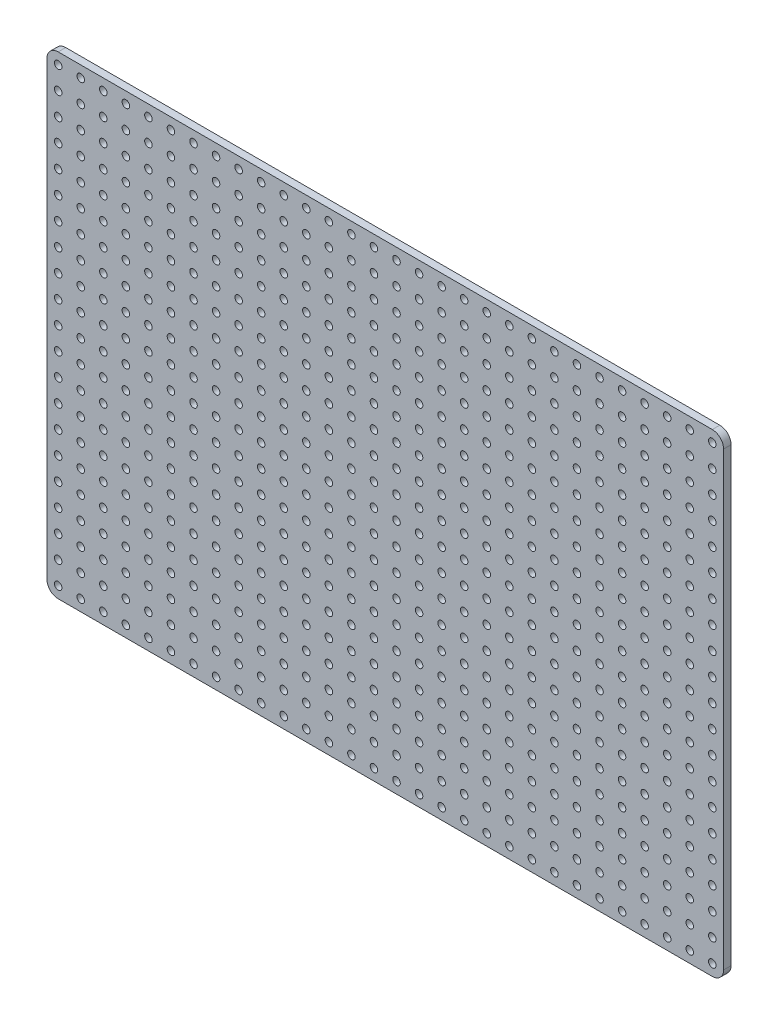
SolidWorks part; units mm, degrees
ref_plane "Alzado" through (0, 0, 0) normal (0, 0, 1) x (1, 0, 0)
ref_plane "Planta" through (0, 0, 0) normal (0, 1, 0) x (1, 0, 0)
ref_plane "Vista lateral" through (0, 0, 0) normal (1, 0, 0) x (0, 0, -1)
sketch "Model" plane through (0, 0, 0) normal (0, 0, 1) x (1, 0, 0)
  line L0 (256.4291, 489.7422) -> (517.4291, 489.7422)
  line L1 (256.4291, 300.7422) -> (517.4291, 300.7422)
  line L2 (251.9291, 305.2422) -> (251.9291, 485.2422)
  line L3 (521.9291, 485.2422) -> (521.9291, 305.2422)
  arc A0 (521.9291, 485.2422) -> (517.4291, 489.7422) centre (517.4291, 485.2422) ccw
  arc A1 (256.4291, 489.7422) -> (251.9291, 485.2422) centre (256.4291, 485.2422) ccw
  arc A2 (517.4291, 300.7422) -> (521.9291, 305.2422) centre (517.4291, 305.2422) ccw
  arc A3 (251.9291, 305.2422) -> (256.4291, 300.7422) centre (256.4291, 305.2422) ccw
  circle A4 centre (256.4291, 485.2422) radius 1.5
  circle A5 centre (256.4291, 476.2422) radius 1.5
  circle A6 centre (256.4291, 467.2422) radius 1.5
  circle A7 centre (256.4291, 458.2422) radius 1.5
  circle A8 centre (256.4291, 449.2422) radius 1.5
  circle A9 centre (256.4291, 440.2422) radius 1.5
  circle A10 centre (256.4291, 431.2422) radius 1.5
  circle A11 centre (256.4291, 422.2422) radius 1.5
  circle A12 centre (256.4291, 413.2422) radius 1.5
  circle A13 centre (256.4291, 404.2422) radius 1.5
  circle A14 centre (256.4291, 395.2422) radius 1.5
  circle A15 centre (256.4291, 386.2422) radius 1.5
  circle A16 centre (256.4291, 377.2422) radius 1.5
  circle A17 centre (256.4291, 368.2422) radius 1.5
  circle A18 centre (256.4291, 359.2422) radius 1.5
  circle A19 centre (256.4291, 350.2422) radius 1.5
  circle A20 centre (256.4291, 341.2422) radius 1.5
  circle A21 centre (256.4291, 332.2422) radius 1.5
  circle A22 centre (256.4291, 323.2422) radius 1.5
  circle A23 centre (256.4291, 314.2422) radius 1.5
  circle A24 centre (256.4291, 305.2422) radius 1.5
  circle A25 centre (265.4291, 485.2422) radius 1.5
  circle A26 centre (265.4291, 476.2422) radius 1.5
  circle A27 centre (265.4291, 467.2422) radius 1.5
  circle A28 centre (265.4291, 458.2422) radius 1.5
  circle A29 centre (265.4291, 449.2422) radius 1.5
  circle A30 centre (265.4291, 440.2422) radius 1.5
  circle A31 centre (265.4291, 431.2422) radius 1.5
  circle A32 centre (265.4291, 422.2422) radius 1.5
  circle A33 centre (265.4291, 413.2422) radius 1.5
  circle A34 centre (265.4291, 404.2422) radius 1.5
  circle A35 centre (265.4291, 395.2422) radius 1.5
  circle A36 centre (265.4291, 386.2422) radius 1.5
  circle A37 centre (265.4291, 377.2422) radius 1.5
  circle A38 centre (265.4291, 368.2422) radius 1.5
  circle A39 centre (265.4291, 359.2422) radius 1.5
  circle A40 centre (265.4291, 350.2422) radius 1.5
  circle A41 centre (265.4291, 341.2422) radius 1.5
  circle A42 centre (265.4291, 332.2422) radius 1.5
  circle A43 centre (265.4291, 323.2422) radius 1.5
  circle A44 centre (265.4291, 314.2422) radius 1.5
  circle A45 centre (265.4291, 305.2422) radius 1.5
  circle A46 centre (274.4291, 485.2422) radius 1.5
  circle A47 centre (274.4291, 476.2422) radius 1.5
  circle A48 centre (274.4291, 467.2422) radius 1.5
  circle A49 centre (274.4291, 458.2422) radius 1.5
  circle A50 centre (274.4291, 449.2422) radius 1.5
  circle A51 centre (274.4291, 440.2422) radius 1.5
  circle A52 centre (274.4291, 431.2422) radius 1.5
  circle A53 centre (274.4291, 422.2422) radius 1.5
  circle A54 centre (274.4291, 413.2422) radius 1.5
  circle A55 centre (274.4291, 404.2422) radius 1.5
  circle A56 centre (274.4291, 395.2422) radius 1.5
  circle A57 centre (274.4291, 386.2422) radius 1.5
  circle A58 centre (274.4291, 377.2422) radius 1.5
  circle A59 centre (274.4291, 368.2422) radius 1.5
  circle A60 centre (274.4291, 359.2422) radius 1.5
  circle A61 centre (274.4291, 350.2422) radius 1.5
  circle A62 centre (274.4291, 341.2422) radius 1.5
  circle A63 centre (274.4291, 332.2422) radius 1.5
  circle A64 centre (274.4291, 323.2422) radius 1.5
  circle A65 centre (274.4291, 314.2422) radius 1.5
  circle A66 centre (274.4291, 305.2422) radius 1.5
  circle A67 centre (283.4291, 485.2422) radius 1.5
  circle A68 centre (283.4291, 476.2422) radius 1.5
  circle A69 centre (283.4291, 467.2422) radius 1.5
  circle A70 centre (283.4291, 458.2422) radius 1.5
  circle A71 centre (283.4291, 449.2422) radius 1.5
  circle A72 centre (283.4291, 440.2422) radius 1.5
  circle A73 centre (283.4291, 431.2422) radius 1.5
  circle A74 centre (283.4291, 422.2422) radius 1.5
  circle A75 centre (283.4291, 413.2422) radius 1.5
  circle A76 centre (283.4291, 404.2422) radius 1.5
  circle A77 centre (283.4291, 395.2422) radius 1.5
  circle A78 centre (283.4291, 386.2422) radius 1.5
  circle A79 centre (283.4291, 377.2422) radius 1.5
  circle A80 centre (283.4291, 368.2422) radius 1.5
  circle A81 centre (283.4291, 359.2422) radius 1.5
  circle A82 centre (283.4291, 350.2422) radius 1.5
  circle A83 centre (283.4291, 341.2422) radius 1.5
  circle A84 centre (283.4291, 332.2422) radius 1.5
  circle A85 centre (283.4291, 323.2422) radius 1.5
  circle A86 centre (283.4291, 314.2422) radius 1.5
  circle A87 centre (283.4291, 305.2422) radius 1.5
  circle A88 centre (292.4291, 485.2422) radius 1.5
  circle A89 centre (292.4291, 476.2422) radius 1.5
  circle A90 centre (292.4291, 467.2422) radius 1.5
  circle A91 centre (292.4291, 458.2422) radius 1.5
  circle A92 centre (292.4291, 449.2422) radius 1.5
  circle A93 centre (292.4291, 440.2422) radius 1.5
  circle A94 centre (292.4291, 431.2422) radius 1.5
  circle A95 centre (292.4291, 422.2422) radius 1.5
  circle A96 centre (292.4291, 413.2422) radius 1.5
  circle A97 centre (292.4291, 404.2422) radius 1.5
  circle A98 centre (292.4291, 395.2422) radius 1.5
  circle A99 centre (292.4291, 386.2422) radius 1.5
  circle A100 centre (292.4291, 377.2422) radius 1.5
  circle A101 centre (292.4291, 368.2422) radius 1.5
  circle A102 centre (292.4291, 359.2422) radius 1.5
  circle A103 centre (292.4291, 350.2422) radius 1.5
  circle A104 centre (292.4291, 341.2422) radius 1.5
  circle A105 centre (292.4291, 332.2422) radius 1.5
  circle A106 centre (292.4291, 323.2422) radius 1.5
  circle A107 centre (292.4291, 314.2422) radius 1.5
  circle A108 centre (292.4291, 305.2422) radius 1.5
  circle A109 centre (301.4291, 485.2422) radius 1.5
  circle A110 centre (301.4291, 476.2422) radius 1.5
  circle A111 centre (301.4291, 467.2422) radius 1.5
  circle A112 centre (301.4291, 458.2422) radius 1.5
  circle A113 centre (301.4291, 449.2422) radius 1.5
  circle A114 centre (301.4291, 440.2422) radius 1.5
  circle A115 centre (301.4291, 431.2422) radius 1.5
  circle A116 centre (301.4291, 422.2422) radius 1.5
  circle A117 centre (301.4291, 413.2422) radius 1.5
  circle A118 centre (301.4291, 404.2422) radius 1.5
  circle A119 centre (301.4291, 395.2422) radius 1.5
  circle A120 centre (301.4291, 386.2422) radius 1.5
  circle A121 centre (301.4291, 377.2422) radius 1.5
  circle A122 centre (301.4291, 368.2422) radius 1.5
  circle A123 centre (301.4291, 359.2422) radius 1.5
  circle A124 centre (301.4291, 350.2422) radius 1.5
  circle A125 centre (301.4291, 341.2422) radius 1.5
  circle A126 centre (301.4291, 332.2422) radius 1.5
  circle A127 centre (301.4291, 323.2422) radius 1.5
  circle A128 centre (301.4291, 314.2422) radius 1.5
  circle A129 centre (301.4291, 305.2422) radius 1.5
  circle A130 centre (310.4291, 485.2422) radius 1.5
  circle A131 centre (310.4291, 476.2422) radius 1.5
  circle A132 centre (310.4291, 467.2422) radius 1.5
  circle A133 centre (310.4291, 458.2422) radius 1.5
  circle A134 centre (310.4291, 449.2422) radius 1.5
  circle A135 centre (310.4291, 440.2422) radius 1.5
  circle A136 centre (310.4291, 431.2422) radius 1.5
  circle A137 centre (310.4291, 422.2422) radius 1.5
  circle A138 centre (310.4291, 413.2422) radius 1.5
  circle A139 centre (310.4291, 404.2422) radius 1.5
  circle A140 centre (310.4291, 395.2422) radius 1.5
  circle A141 centre (310.4291, 386.2422) radius 1.5
  circle A142 centre (310.4291, 377.2422) radius 1.5
  circle A143 centre (310.4291, 368.2422) radius 1.5
  circle A144 centre (310.4291, 359.2422) radius 1.5
  circle A145 centre (310.4291, 350.2422) radius 1.5
  circle A146 centre (310.4291, 341.2422) radius 1.5
  circle A147 centre (310.4291, 332.2422) radius 1.5
  circle A148 centre (310.4291, 323.2422) radius 1.5
  circle A149 centre (310.4291, 314.2422) radius 1.5
  circle A150 centre (310.4291, 305.2422) radius 1.5
  circle A151 centre (319.4291, 485.2422) radius 1.5
  circle A152 centre (319.4291, 476.2422) radius 1.5
  circle A153 centre (319.4291, 467.2422) radius 1.5
  circle A154 centre (319.4291, 458.2422) radius 1.5
  circle A155 centre (319.4291, 449.2422) radius 1.5
  circle A156 centre (319.4291, 440.2422) radius 1.5
  circle A157 centre (319.4291, 431.2422) radius 1.5
  circle A158 centre (319.4291, 422.2422) radius 1.5
  circle A159 centre (319.4291, 413.2422) radius 1.5
  circle A160 centre (319.4291, 404.2422) radius 1.5
  circle A161 centre (319.4291, 395.2422) radius 1.5
  circle A162 centre (319.4291, 386.2422) radius 1.5
  circle A163 centre (319.4291, 377.2422) radius 1.5
  circle A164 centre (319.4291, 368.2422) radius 1.5
  circle A165 centre (319.4291, 359.2422) radius 1.5
  circle A166 centre (319.4291, 350.2422) radius 1.5
  circle A167 centre (319.4291, 341.2422) radius 1.5
  circle A168 centre (319.4291, 332.2422) radius 1.5
  circle A169 centre (319.4291, 323.2422) radius 1.5
  circle A170 centre (319.4291, 314.2422) radius 1.5
  circle A171 centre (319.4291, 305.2422) radius 1.5
  circle A172 centre (328.4291, 485.2422) radius 1.5
  circle A173 centre (328.4291, 476.2422) radius 1.5
  circle A174 centre (328.4291, 467.2422) radius 1.5
  circle A175 centre (328.4291, 458.2422) radius 1.5
  circle A176 centre (328.4291, 449.2422) radius 1.5
  circle A177 centre (328.4291, 440.2422) radius 1.5
  circle A178 centre (328.4291, 431.2422) radius 1.5
  circle A179 centre (328.4291, 422.2422) radius 1.5
  circle A180 centre (328.4291, 413.2422) radius 1.5
  circle A181 centre (328.4291, 404.2422) radius 1.5
  circle A182 centre (328.4291, 395.2422) radius 1.5
  circle A183 centre (328.4291, 386.2422) radius 1.5
  circle A184 centre (328.4291, 377.2422) radius 1.5
  circle A185 centre (328.4291, 368.2422) radius 1.5
  circle A186 centre (328.4291, 359.2422) radius 1.5
  circle A187 centre (328.4291, 350.2422) radius 1.5
  circle A188 centre (328.4291, 341.2422) radius 1.5
  circle A189 centre (328.4291, 332.2422) radius 1.5
  circle A190 centre (328.4291, 323.2422) radius 1.5
  circle A191 centre (328.4291, 314.2422) radius 1.5
  circle A192 centre (328.4291, 305.2422) radius 1.5
  circle A193 centre (337.4291, 485.2422) radius 1.5
  circle A194 centre (337.4291, 476.2422) radius 1.5
  circle A195 centre (337.4291, 467.2422) radius 1.5
  circle A196 centre (337.4291, 458.2422) radius 1.5
  circle A197 centre (337.4291, 449.2422) radius 1.5
  circle A198 centre (337.4291, 440.2422) radius 1.5
  circle A199 centre (337.4291, 431.2422) radius 1.5
  circle A200 centre (337.4291, 422.2422) radius 1.5
  circle A201 centre (337.4291, 413.2422) radius 1.5
  circle A202 centre (337.4291, 404.2422) radius 1.5
  circle A203 centre (337.4291, 395.2422) radius 1.5
  circle A204 centre (337.4291, 386.2422) radius 1.5
  circle A205 centre (337.4291, 377.2422) radius 1.5
  circle A206 centre (337.4291, 368.2422) radius 1.5
  circle A207 centre (337.4291, 359.2422) radius 1.5
  circle A208 centre (337.4291, 350.2422) radius 1.5
  circle A209 centre (337.4291, 341.2422) radius 1.5
  circle A210 centre (337.4291, 332.2422) radius 1.5
  circle A211 centre (337.4291, 323.2422) radius 1.5
  circle A212 centre (337.4291, 314.2422) radius 1.5
  circle A213 centre (337.4291, 305.2422) radius 1.5
  circle A214 centre (346.4291, 485.2422) radius 1.5
  circle A215 centre (346.4291, 476.2422) radius 1.5
  circle A216 centre (346.4291, 467.2422) radius 1.5
  circle A217 centre (346.4291, 458.2422) radius 1.5
  circle A218 centre (346.4291, 449.2422) radius 1.5
  circle A219 centre (346.4291, 440.2422) radius 1.5
  circle A220 centre (346.4291, 431.2422) radius 1.5
  circle A221 centre (346.4291, 422.2422) radius 1.5
  circle A222 centre (346.4291, 413.2422) radius 1.5
  circle A223 centre (346.4291, 404.2422) radius 1.5
  circle A224 centre (346.4291, 395.2422) radius 1.5
  circle A225 centre (346.4291, 386.2422) radius 1.5
  circle A226 centre (346.4291, 377.2422) radius 1.5
  circle A227 centre (346.4291, 368.2422) radius 1.5
  circle A228 centre (346.4291, 359.2422) radius 1.5
  circle A229 centre (346.4291, 350.2422) radius 1.5
  circle A230 centre (346.4291, 341.2422) radius 1.5
  circle A231 centre (346.4291, 332.2422) radius 1.5
  circle A232 centre (346.4291, 323.2422) radius 1.5
  circle A233 centre (346.4291, 314.2422) radius 1.5
  circle A234 centre (346.4291, 305.2422) radius 1.5
  circle A235 centre (355.4291, 485.2422) radius 1.5
  circle A236 centre (355.4291, 476.2422) radius 1.5
  circle A237 centre (355.4291, 467.2422) radius 1.5
  circle A238 centre (355.4291, 458.2422) radius 1.5
  circle A239 centre (355.4291, 449.2422) radius 1.5
  circle A240 centre (355.4291, 440.2422) radius 1.5
  circle A241 centre (355.4291, 431.2422) radius 1.5
  circle A242 centre (355.4291, 422.2422) radius 1.5
  circle A243 centre (355.4291, 413.2422) radius 1.5
  circle A244 centre (355.4291, 404.2422) radius 1.5
  circle A245 centre (355.4291, 395.2422) radius 1.5
  circle A246 centre (355.4291, 386.2422) radius 1.5
  circle A247 centre (355.4291, 377.2422) radius 1.5
  circle A248 centre (355.4291, 368.2422) radius 1.5
  circle A249 centre (355.4291, 359.2422) radius 1.5
  circle A250 centre (355.4291, 350.2422) radius 1.5
  circle A251 centre (355.4291, 341.2422) radius 1.5
  circle A252 centre (355.4291, 332.2422) radius 1.5
  circle A253 centre (355.4291, 323.2422) radius 1.5
  circle A254 centre (355.4291, 314.2422) radius 1.5
  circle A255 centre (355.4291, 305.2422) radius 1.5
  circle A256 centre (364.4291, 485.2422) radius 1.5
  circle A257 centre (364.4291, 476.2422) radius 1.5
  circle A258 centre (364.4291, 467.2422) radius 1.5
  circle A259 centre (364.4291, 458.2422) radius 1.5
  circle A260 centre (364.4291, 449.2422) radius 1.5
  circle A261 centre (364.4291, 440.2422) radius 1.5
  circle A262 centre (364.4291, 431.2422) radius 1.5
  circle A263 centre (364.4291, 422.2422) radius 1.5
  circle A264 centre (364.4291, 413.2422) radius 1.5
  circle A265 centre (364.4291, 404.2422) radius 1.5
  circle A266 centre (364.4291, 395.2422) radius 1.5
  circle A267 centre (364.4291, 386.2422) radius 1.5
  circle A268 centre (364.4291, 377.2422) radius 1.5
  circle A269 centre (364.4291, 368.2422) radius 1.5
  circle A270 centre (364.4291, 359.2422) radius 1.5
  circle A271 centre (364.4291, 350.2422) radius 1.5
  circle A272 centre (364.4291, 341.2422) radius 1.5
  circle A273 centre (364.4291, 332.2422) radius 1.5
  circle A274 centre (364.4291, 323.2422) radius 1.5
  circle A275 centre (364.4291, 314.2422) radius 1.5
  circle A276 centre (364.4291, 305.2422) radius 1.5
  circle A277 centre (373.4291, 485.2422) radius 1.5
  circle A278 centre (373.4291, 476.2422) radius 1.5
  circle A279 centre (373.4291, 467.2422) radius 1.5
  circle A280 centre (373.4291, 458.2422) radius 1.5
  circle A281 centre (373.4291, 449.2422) radius 1.5
  circle A282 centre (373.4291, 440.2422) radius 1.5
  circle A283 centre (373.4291, 431.2422) radius 1.5
  circle A284 centre (373.4291, 422.2422) radius 1.5
  circle A285 centre (373.4291, 413.2422) radius 1.5
  circle A286 centre (373.4291, 404.2422) radius 1.5
  circle A287 centre (373.4291, 395.2422) radius 1.5
  circle A288 centre (373.4291, 386.2422) radius 1.5
  circle A289 centre (373.4291, 377.2422) radius 1.5
  circle A290 centre (373.4291, 368.2422) radius 1.5
  circle A291 centre (373.4291, 359.2422) radius 1.5
  circle A292 centre (373.4291, 350.2422) radius 1.5
  circle A293 centre (373.4291, 341.2422) radius 1.5
  circle A294 centre (373.4291, 332.2422) radius 1.5
  circle A295 centre (373.4291, 323.2422) radius 1.5
  circle A296 centre (373.4291, 314.2422) radius 1.5
  circle A297 centre (373.4291, 305.2422) radius 1.5
  circle A298 centre (382.4291, 485.2422) radius 1.5
  circle A299 centre (382.4291, 476.2422) radius 1.5
  circle A300 centre (382.4291, 467.2422) radius 1.5
  circle A301 centre (382.4291, 458.2422) radius 1.5
  circle A302 centre (382.4291, 449.2422) radius 1.5
  circle A303 centre (382.4291, 440.2422) radius 1.5
  circle A304 centre (382.4291, 431.2422) radius 1.5
  circle A305 centre (382.4291, 422.2422) radius 1.5
  circle A306 centre (382.4291, 413.2422) radius 1.5
  circle A307 centre (382.4291, 404.2422) radius 1.5
  circle A308 centre (382.4291, 395.2422) radius 1.5
  circle A309 centre (382.4291, 386.2422) radius 1.5
  circle A310 centre (382.4291, 377.2422) radius 1.5
  circle A311 centre (382.4291, 368.2422) radius 1.5
  circle A312 centre (382.4291, 359.2422) radius 1.5
  circle A313 centre (382.4291, 350.2422) radius 1.5
  circle A314 centre (382.4291, 341.2422) radius 1.5
  circle A315 centre (382.4291, 332.2422) radius 1.5
  circle A316 centre (382.4291, 323.2422) radius 1.5
  circle A317 centre (382.4291, 314.2422) radius 1.5
  circle A318 centre (382.4291, 305.2422) radius 1.5
  circle A319 centre (391.4291, 485.2422) radius 1.5
  circle A320 centre (391.4291, 476.2422) radius 1.5
  circle A321 centre (391.4291, 467.2422) radius 1.5
  circle A322 centre (391.4291, 458.2422) radius 1.5
  circle A323 centre (391.4291, 449.2422) radius 1.5
  circle A324 centre (391.4291, 440.2422) radius 1.5
  circle A325 centre (391.4291, 431.2422) radius 1.5
  circle A326 centre (391.4291, 422.2422) radius 1.5
  circle A327 centre (391.4291, 413.2422) radius 1.5
  circle A328 centre (391.4291, 404.2422) radius 1.5
  circle A329 centre (391.4291, 395.2422) radius 1.5
  circle A330 centre (391.4291, 386.2422) radius 1.5
  circle A331 centre (391.4291, 377.2422) radius 1.5
  circle A332 centre (391.4291, 368.2422) radius 1.5
  circle A333 centre (391.4291, 359.2422) radius 1.5
  circle A334 centre (391.4291, 350.2422) radius 1.5
  circle A335 centre (391.4291, 341.2422) radius 1.5
  circle A336 centre (391.4291, 332.2422) radius 1.5
  circle A337 centre (391.4291, 323.2422) radius 1.5
  circle A338 centre (391.4291, 314.2422) radius 1.5
  circle A339 centre (391.4291, 305.2422) radius 1.5
  circle A340 centre (400.4291, 485.2422) radius 1.5
  circle A341 centre (400.4291, 476.2422) radius 1.5
  circle A342 centre (400.4291, 467.2422) radius 1.5
  circle A343 centre (400.4291, 458.2422) radius 1.5
  circle A344 centre (400.4291, 449.2422) radius 1.5
  circle A345 centre (400.4291, 440.2422) radius 1.5
  circle A346 centre (400.4291, 431.2422) radius 1.5
  circle A347 centre (400.4291, 422.2422) radius 1.5
  circle A348 centre (400.4291, 413.2422) radius 1.5
  circle A349 centre (400.4291, 404.2422) radius 1.5
  circle A350 centre (400.4291, 395.2422) radius 1.5
  circle A351 centre (400.4291, 386.2422) radius 1.5
  circle A352 centre (400.4291, 377.2422) radius 1.5
  circle A353 centre (400.4291, 368.2422) radius 1.5
  circle A354 centre (400.4291, 359.2422) radius 1.5
  circle A355 centre (400.4291, 350.2422) radius 1.5
  circle A356 centre (400.4291, 341.2422) radius 1.5
  circle A357 centre (400.4291, 332.2422) radius 1.5
  circle A358 centre (400.4291, 323.2422) radius 1.5
  circle A359 centre (400.4291, 314.2422) radius 1.5
  circle A360 centre (400.4291, 305.2422) radius 1.5
  circle A361 centre (409.4291, 485.2422) radius 1.5
  circle A362 centre (409.4291, 476.2422) radius 1.5
  circle A363 centre (409.4291, 467.2422) radius 1.5
  circle A364 centre (409.4291, 458.2422) radius 1.5
  circle A365 centre (409.4291, 449.2422) radius 1.5
  circle A366 centre (409.4291, 440.2422) radius 1.5
  circle A367 centre (409.4291, 431.2422) radius 1.5
  circle A368 centre (409.4291, 422.2422) radius 1.5
  circle A369 centre (409.4291, 413.2422) radius 1.5
  circle A370 centre (409.4291, 404.2422) radius 1.5
  circle A371 centre (409.4291, 395.2422) radius 1.5
  circle A372 centre (409.4291, 386.2422) radius 1.5
  circle A373 centre (409.4291, 377.2422) radius 1.5
  circle A374 centre (409.4291, 368.2422) radius 1.5
  circle A375 centre (409.4291, 359.2422) radius 1.5
  circle A376 centre (409.4291, 350.2422) radius 1.5
  circle A377 centre (409.4291, 341.2422) radius 1.5
  circle A378 centre (409.4291, 332.2422) radius 1.5
  circle A379 centre (409.4291, 323.2422) radius 1.5
  circle A380 centre (409.4291, 314.2422) radius 1.5
  circle A381 centre (409.4291, 305.2422) radius 1.5
  circle A382 centre (418.4291, 485.2422) radius 1.5
  circle A383 centre (418.4291, 476.2422) radius 1.5
  circle A384 centre (418.4291, 467.2422) radius 1.5
  circle A385 centre (418.4291, 458.2422) radius 1.5
  circle A386 centre (418.4291, 449.2422) radius 1.5
  circle A387 centre (418.4291, 440.2422) radius 1.5
  circle A388 centre (418.4291, 431.2422) radius 1.5
  circle A389 centre (418.4291, 422.2422) radius 1.5
  circle A390 centre (418.4291, 413.2422) radius 1.5
  circle A391 centre (418.4291, 404.2422) radius 1.5
  circle A392 centre (418.4291, 395.2422) radius 1.5
  circle A393 centre (418.4291, 386.2422) radius 1.5
  circle A394 centre (418.4291, 377.2422) radius 1.5
  circle A395 centre (418.4291, 368.2422) radius 1.5
  circle A396 centre (418.4291, 359.2422) radius 1.5
  circle A397 centre (418.4291, 350.2422) radius 1.5
  circle A398 centre (418.4291, 341.2422) radius 1.5
  circle A399 centre (418.4291, 332.2422) radius 1.5
  circle A400 centre (418.4291, 323.2422) radius 1.5
  circle A401 centre (418.4291, 314.2422) radius 1.5
  circle A402 centre (418.4291, 305.2422) radius 1.5
  circle A403 centre (427.4291, 485.2422) radius 1.5
  circle A404 centre (427.4291, 476.2422) radius 1.5
  circle A405 centre (427.4291, 467.2422) radius 1.5
  circle A406 centre (427.4291, 458.2422) radius 1.5
  circle A407 centre (427.4291, 449.2422) radius 1.5
  circle A408 centre (427.4291, 440.2422) radius 1.5
  circle A409 centre (427.4291, 431.2422) radius 1.5
  circle A410 centre (427.4291, 422.2422) radius 1.5
  circle A411 centre (427.4291, 413.2422) radius 1.5
  circle A412 centre (427.4291, 404.2422) radius 1.5
  circle A413 centre (427.4291, 395.2422) radius 1.5
  circle A414 centre (427.4291, 386.2422) radius 1.5
  circle A415 centre (427.4291, 377.2422) radius 1.5
  circle A416 centre (427.4291, 368.2422) radius 1.5
  circle A417 centre (427.4291, 359.2422) radius 1.5
  circle A418 centre (427.4291, 350.2422) radius 1.5
  circle A419 centre (427.4291, 341.2422) radius 1.5
  circle A420 centre (427.4291, 332.2422) radius 1.5
  circle A421 centre (427.4291, 323.2422) radius 1.5
  circle A422 centre (427.4291, 314.2422) radius 1.5
  circle A423 centre (427.4291, 305.2422) radius 1.5
  circle A424 centre (436.4291, 485.2422) radius 1.5
  circle A425 centre (436.4291, 476.2422) radius 1.5
  circle A426 centre (436.4291, 467.2422) radius 1.5
  circle A427 centre (436.4291, 458.2422) radius 1.5
  circle A428 centre (436.4291, 449.2422) radius 1.5
  circle A429 centre (436.4291, 440.2422) radius 1.5
  circle A430 centre (436.4291, 431.2422) radius 1.5
  circle A431 centre (436.4291, 422.2422) radius 1.5
  circle A432 centre (436.4291, 413.2422) radius 1.5
  circle A433 centre (436.4291, 404.2422) radius 1.5
  circle A434 centre (436.4291, 395.2422) radius 1.5
  circle A435 centre (436.4291, 386.2422) radius 1.5
  circle A436 centre (436.4291, 377.2422) radius 1.5
  circle A437 centre (436.4291, 368.2422) radius 1.5
  circle A438 centre (436.4291, 359.2422) radius 1.5
  circle A439 centre (436.4291, 350.2422) radius 1.5
  circle A440 centre (436.4291, 341.2422) radius 1.5
  circle A441 centre (436.4291, 332.2422) radius 1.5
  circle A442 centre (436.4291, 323.2422) radius 1.5
  circle A443 centre (436.4291, 314.2422) radius 1.5
  circle A444 centre (436.4291, 305.2422) radius 1.5
  circle A445 centre (445.4291, 485.2422) radius 1.5
  circle A446 centre (445.4291, 476.2422) radius 1.5
  circle A447 centre (445.4291, 467.2422) radius 1.5
  circle A448 centre (445.4291, 458.2422) radius 1.5
  circle A449 centre (445.4291, 449.2422) radius 1.5
  circle A450 centre (445.4291, 440.2422) radius 1.5
  circle A451 centre (445.4291, 431.2422) radius 1.5
  circle A452 centre (445.4291, 422.2422) radius 1.5
  circle A453 centre (445.4291, 413.2422) radius 1.5
  circle A454 centre (445.4291, 404.2422) radius 1.5
  circle A455 centre (445.4291, 395.2422) radius 1.5
  circle A456 centre (445.4291, 386.2422) radius 1.5
  circle A457 centre (445.4291, 377.2422) radius 1.5
  circle A458 centre (445.4291, 368.2422) radius 1.5
  circle A459 centre (445.4291, 359.2422) radius 1.5
  circle A460 centre (445.4291, 350.2422) radius 1.5
  circle A461 centre (445.4291, 341.2422) radius 1.5
  circle A462 centre (445.4291, 332.2422) radius 1.5
  circle A463 centre (445.4291, 323.2422) radius 1.5
  circle A464 centre (445.4291, 314.2422) radius 1.5
  circle A465 centre (445.4291, 305.2422) radius 1.5
  circle A466 centre (454.4291, 485.2422) radius 1.5
  circle A467 centre (454.4291, 476.2422) radius 1.5
  circle A468 centre (454.4291, 467.2422) radius 1.5
  circle A469 centre (454.4291, 458.2422) radius 1.5
  circle A470 centre (454.4291, 449.2422) radius 1.5
  circle A471 centre (454.4291, 440.2422) radius 1.5
  circle A472 centre (454.4291, 431.2422) radius 1.5
  circle A473 centre (454.4291, 422.2422) radius 1.5
  circle A474 centre (454.4291, 413.2422) radius 1.5
  circle A475 centre (454.4291, 404.2422) radius 1.5
  circle A476 centre (454.4291, 395.2422) radius 1.5
  circle A477 centre (454.4291, 386.2422) radius 1.5
  circle A478 centre (454.4291, 377.2422) radius 1.5
  circle A479 centre (454.4291, 368.2422) radius 1.5
  circle A480 centre (454.4291, 359.2422) radius 1.5
  circle A481 centre (454.4291, 350.2422) radius 1.5
  circle A482 centre (454.4291, 341.2422) radius 1.5
  circle A483 centre (454.4291, 332.2422) radius 1.5
  circle A484 centre (454.4291, 323.2422) radius 1.5
  circle A485 centre (454.4291, 314.2422) radius 1.5
  circle A486 centre (454.4291, 305.2422) radius 1.5
  circle A487 centre (463.4291, 485.2422) radius 1.5
  circle A488 centre (463.4291, 476.2422) radius 1.5
  circle A489 centre (463.4291, 467.2422) radius 1.5
  circle A490 centre (463.4291, 458.2422) radius 1.5
  circle A491 centre (463.4291, 449.2422) radius 1.5
  circle A492 centre (463.4291, 440.2422) radius 1.5
  circle A493 centre (463.4291, 431.2422) radius 1.5
  circle A494 centre (463.4291, 422.2422) radius 1.5
  circle A495 centre (463.4291, 413.2422) radius 1.5
  circle A496 centre (463.4291, 404.2422) radius 1.5
  circle A497 centre (463.4291, 395.2422) radius 1.5
  circle A498 centre (463.4291, 386.2422) radius 1.5
  circle A499 centre (463.4291, 377.2422) radius 1.5
  circle A500 centre (463.4291, 368.2422) radius 1.5
  circle A501 centre (463.4291, 359.2422) radius 1.5
  circle A502 centre (463.4291, 350.2422) radius 1.5
  circle A503 centre (463.4291, 341.2422) radius 1.5
  circle A504 centre (463.4291, 332.2422) radius 1.5
  circle A505 centre (463.4291, 323.2422) radius 1.5
  circle A506 centre (463.4291, 314.2422) radius 1.5
  circle A507 centre (463.4291, 305.2422) radius 1.5
  circle A508 centre (472.4291, 485.2422) radius 1.5
  circle A509 centre (472.4291, 476.2422) radius 1.5
  circle A510 centre (472.4291, 467.2422) radius 1.5
  circle A511 centre (472.4291, 458.2422) radius 1.5
  circle A512 centre (472.4291, 449.2422) radius 1.5
  circle A513 centre (472.4291, 440.2422) radius 1.5
  circle A514 centre (472.4291, 431.2422) radius 1.5
  circle A515 centre (472.4291, 422.2422) radius 1.5
  circle A516 centre (472.4291, 413.2422) radius 1.5
  circle A517 centre (472.4291, 404.2422) radius 1.5
  circle A518 centre (472.4291, 395.2422) radius 1.5
  circle A519 centre (472.4291, 386.2422) radius 1.5
  circle A520 centre (472.4291, 377.2422) radius 1.5
  circle A521 centre (472.4291, 368.2422) radius 1.5
  circle A522 centre (472.4291, 359.2422) radius 1.5
  circle A523 centre (472.4291, 350.2422) radius 1.5
  circle A524 centre (472.4291, 341.2422) radius 1.5
  circle A525 centre (472.4291, 332.2422) radius 1.5
  circle A526 centre (472.4291, 323.2422) radius 1.5
  circle A527 centre (472.4291, 314.2422) radius 1.5
  circle A528 centre (472.4291, 305.2422) radius 1.5
  circle A529 centre (481.4291, 485.2422) radius 1.5
  circle A530 centre (481.4291, 476.2422) radius 1.5
  circle A531 centre (481.4291, 467.2422) radius 1.5
  circle A532 centre (481.4291, 458.2422) radius 1.5
  circle A533 centre (481.4291, 449.2422) radius 1.5
  circle A534 centre (481.4291, 440.2422) radius 1.5
  circle A535 centre (481.4291, 431.2422) radius 1.5
  circle A536 centre (481.4291, 422.2422) radius 1.5
  circle A537 centre (481.4291, 413.2422) radius 1.5
  circle A538 centre (481.4291, 404.2422) radius 1.5
  circle A539 centre (481.4291, 395.2422) radius 1.5
  circle A540 centre (481.4291, 386.2422) radius 1.5
  circle A541 centre (481.4291, 377.2422) radius 1.5
  circle A542 centre (481.4291, 368.2422) radius 1.5
  circle A543 centre (481.4291, 359.2422) radius 1.5
  circle A544 centre (481.4291, 350.2422) radius 1.5
  circle A545 centre (481.4291, 341.2422) radius 1.5
  circle A546 centre (481.4291, 332.2422) radius 1.5
  circle A547 centre (481.4291, 323.2422) radius 1.5
  circle A548 centre (481.4291, 314.2422) radius 1.5
  circle A549 centre (481.4291, 305.2422) radius 1.5
  circle A550 centre (490.4291, 485.2422) radius 1.5
  circle A551 centre (490.4291, 476.2422) radius 1.5
  circle A552 centre (490.4291, 467.2422) radius 1.5
  circle A553 centre (490.4291, 458.2422) radius 1.5
  circle A554 centre (490.4291, 449.2422) radius 1.5
  circle A555 centre (490.4291, 440.2422) radius 1.5
  circle A556 centre (490.4291, 431.2422) radius 1.5
  circle A557 centre (490.4291, 422.2422) radius 1.5
  circle A558 centre (490.4291, 413.2422) radius 1.5
  circle A559 centre (490.4291, 404.2422) radius 1.5
  circle A560 centre (490.4291, 395.2422) radius 1.5
  circle A561 centre (490.4291, 386.2422) radius 1.5
  circle A562 centre (490.4291, 377.2422) radius 1.5
  circle A563 centre (490.4291, 368.2422) radius 1.5
  circle A564 centre (490.4291, 359.2422) radius 1.5
  circle A565 centre (490.4291, 350.2422) radius 1.5
  circle A566 centre (490.4291, 341.2422) radius 1.5
  circle A567 centre (490.4291, 332.2422) radius 1.5
  circle A568 centre (490.4291, 323.2422) radius 1.5
  circle A569 centre (490.4291, 314.2422) radius 1.5
  circle A570 centre (490.4291, 305.2422) radius 1.5
  circle A571 centre (499.4291, 485.2422) radius 1.5
  circle A572 centre (499.4291, 476.2422) radius 1.5
  circle A573 centre (499.4291, 467.2422) radius 1.5
  circle A574 centre (499.4291, 458.2422) radius 1.5
  circle A575 centre (499.4291, 449.2422) radius 1.5
  circle A576 centre (499.4291, 440.2422) radius 1.5
  circle A577 centre (499.4291, 431.2422) radius 1.5
  circle A578 centre (499.4291, 422.2422) radius 1.5
  circle A579 centre (499.4291, 413.2422) radius 1.5
  circle A580 centre (499.4291, 404.2422) radius 1.5
  circle A581 centre (499.4291, 395.2422) radius 1.5
  circle A582 centre (499.4291, 386.2422) radius 1.5
  circle A583 centre (499.4291, 377.2422) radius 1.5
  circle A584 centre (499.4291, 368.2422) radius 1.5
  circle A585 centre (499.4291, 359.2422) radius 1.5
  circle A586 centre (499.4291, 350.2422) radius 1.5
  circle A587 centre (499.4291, 341.2422) radius 1.5
  circle A588 centre (499.4291, 332.2422) radius 1.5
  circle A589 centre (499.4291, 323.2422) radius 1.5
  circle A590 centre (499.4291, 314.2422) radius 1.5
  circle A591 centre (499.4291, 305.2422) radius 1.5
  circle A592 centre (508.4291, 485.2422) radius 1.5
  circle A593 centre (508.4291, 476.2422) radius 1.5
  circle A594 centre (508.4291, 467.2422) radius 1.5
  circle A595 centre (508.4291, 458.2422) radius 1.5
  circle A596 centre (508.4291, 449.2422) radius 1.5
  circle A597 centre (508.4291, 440.2422) radius 1.5
  circle A598 centre (508.4291, 431.2422) radius 1.5
  circle A599 centre (508.4291, 422.2422) radius 1.5
  circle A600 centre (508.4291, 413.2422) radius 1.5
  circle A601 centre (508.4291, 404.2422) radius 1.5
  circle A602 centre (508.4291, 395.2422) radius 1.5
  circle A603 centre (508.4291, 386.2422) radius 1.5
  circle A604 centre (508.4291, 377.2422) radius 1.5
  circle A605 centre (508.4291, 368.2422) radius 1.5
  circle A606 centre (508.4291, 359.2422) radius 1.5
  circle A607 centre (508.4291, 350.2422) radius 1.5
  circle A608 centre (508.4291, 341.2422) radius 1.5
  circle A609 centre (508.4291, 332.2422) radius 1.5
  circle A610 centre (508.4291, 323.2422) radius 1.5
  circle A611 centre (508.4291, 314.2422) radius 1.5
  circle A612 centre (508.4291, 305.2422) radius 1.5
  circle A613 centre (517.4291, 485.2422) radius 1.5
  circle A614 centre (517.4291, 476.2422) radius 1.5
  circle A615 centre (517.4291, 467.2422) radius 1.5
  circle A616 centre (517.4291, 458.2422) radius 1.5
  circle A617 centre (517.4291, 449.2422) radius 1.5
  circle A618 centre (517.4291, 440.2422) radius 1.5
  circle A619 centre (517.4291, 431.2422) radius 1.5
  circle A620 centre (517.4291, 422.2422) radius 1.5
  circle A621 centre (517.4291, 413.2422) radius 1.5
  circle A622 centre (517.4291, 404.2422) radius 1.5
  circle A623 centre (517.4291, 395.2422) radius 1.5
  circle A624 centre (517.4291, 386.2422) radius 1.5
  circle A625 centre (517.4291, 377.2422) radius 1.5
  circle A626 centre (517.4291, 368.2422) radius 1.5
  circle A627 centre (517.4291, 359.2422) radius 1.5
  circle A628 centre (517.4291, 350.2422) radius 1.5
  circle A629 centre (517.4291, 341.2422) radius 1.5
  circle A630 centre (517.4291, 332.2422) radius 1.5
  circle A631 centre (517.4291, 323.2422) radius 1.5
  circle A632 centre (517.4291, 314.2422) radius 1.5
  circle A633 centre (517.4291, 305.2422) radius 1.5
extrude "Saliente-Extruir1" add sketch "Model" along normal blind 3
